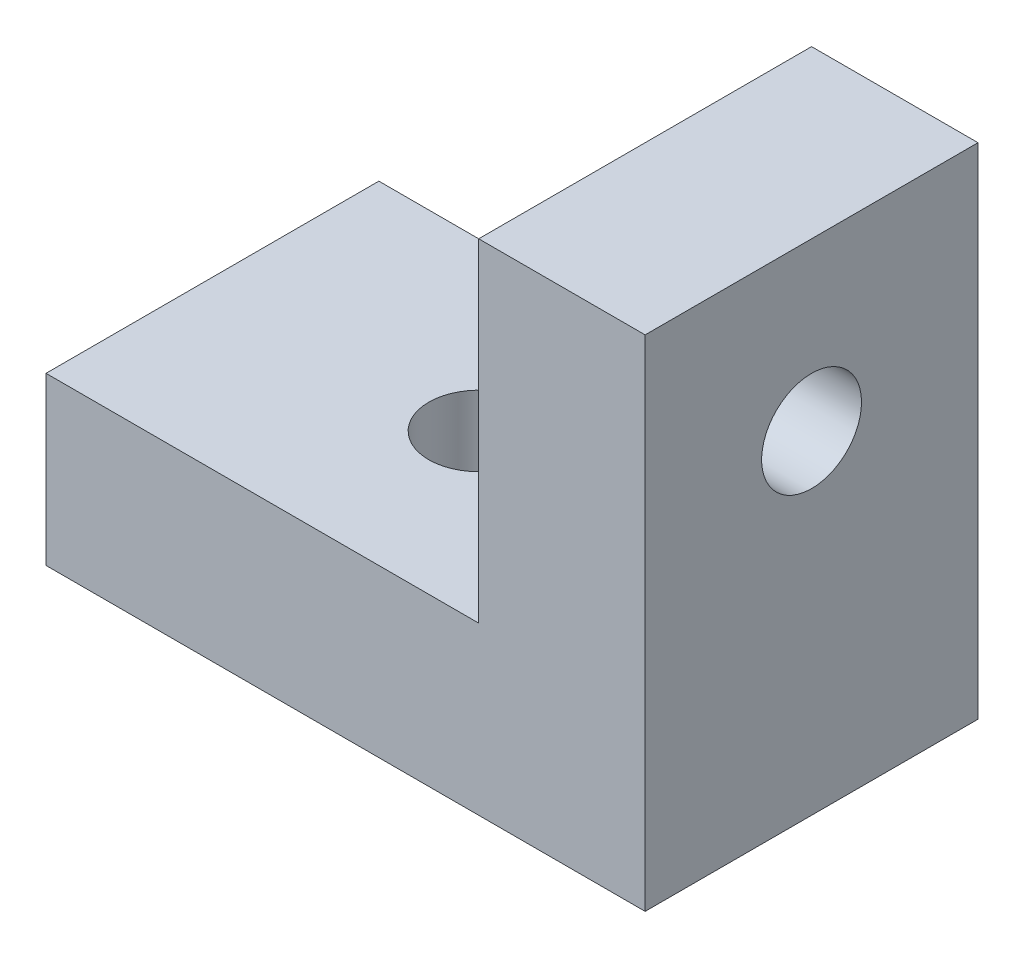
SolidWorks part; units mm, degrees
ref_plane "前视基准面" through (0, 0, 0) normal (0, 0, 1) x (1, 0, 0)
ref_plane "上视基准面" through (0, 0, 0) normal (0, 1, 0) x (1, 0, 0)
ref_plane "右视基准面" through (0, 0, 0) normal (1, 0, 0) x (0, 0, -1)
sketch "草图1" plane through (0, 0, 0) normal (0, 0, 1) x (1, 0, 0)
  line L0 (0, 0) -> (0, 15)
  line L1 (0, 15) -> (-5, 15)
  line L2 (-5, 15) -> (-5, 5)
  line L3 (-5, 5) -> (-18, 5)
  line L4 (-18, 5) -> (-18, 0)
  line L5 (-18, 0) -> (0, 0)
  dimension "D1" = 15
  dimension "D2" = 18
  dimension "D3" = 5
extrude "凸台-拉伸1" add sketch "草图1" along normal blind 10
sketch "草图2" plane through (0, 0, 0) normal (1, 0, 0) x (0, 0, -1)
  line L0 (-10, 15) -> (0, 15) construction
  line L1 (-5, 6.8246) -> (-2.25, 8.4123)
  line L2 (-2.25, 8.4123) -> (-2.25, 11.5877)
  line L3 (-2.25, 11.5877) -> (-5, 13.1754)
  line L4 (-5, 13.1754) -> (-7.75, 11.5877)
  line L5 (-7.75, 11.5877) -> (-7.75, 8.4123)
  line L6 (-7.75, 8.4123) -> (-5, 6.8246)
  line L7 (-10, 0) -> (0, 0) construction
  circle A0 centre (-5, 10) radius 1.5
  circle A1 centre (-5, 10) radius 2.75 construction
  point P2 (0, 0)
  point P12 (-5, 15)
  dimension "D1" = 10
  dimension "D2" = 3
  dimension "D3" = 5.5
extrude "切除-拉伸1" cut sketch "草图2" against normal up to next contours A0 region at (0, 10, 5)
extrude "切除-拉伸2" cut sketch "草图2<3>" along normal blind 2 from surface starting at face at (-5, 11.5, 5)
sketch "草图2<3>" plane through (0, 0, 0) normal (1, 0, 0) x (0, 0, -1) same geometry as "草图2"
sketch "草图3" plane through (0, 5, 0) normal (0, 1, 0) x (1, 0, 0)
  line L0 (-18, -10) -> (-18, 0) construction
  circle A0 centre (-10, -5) radius 1.5
  point P4 (-18, -5)
  dimension "D1" = 10
  dimension "D2" = 3
extrude "切除-拉伸3" cut sketch "草图3" against normal up to next
